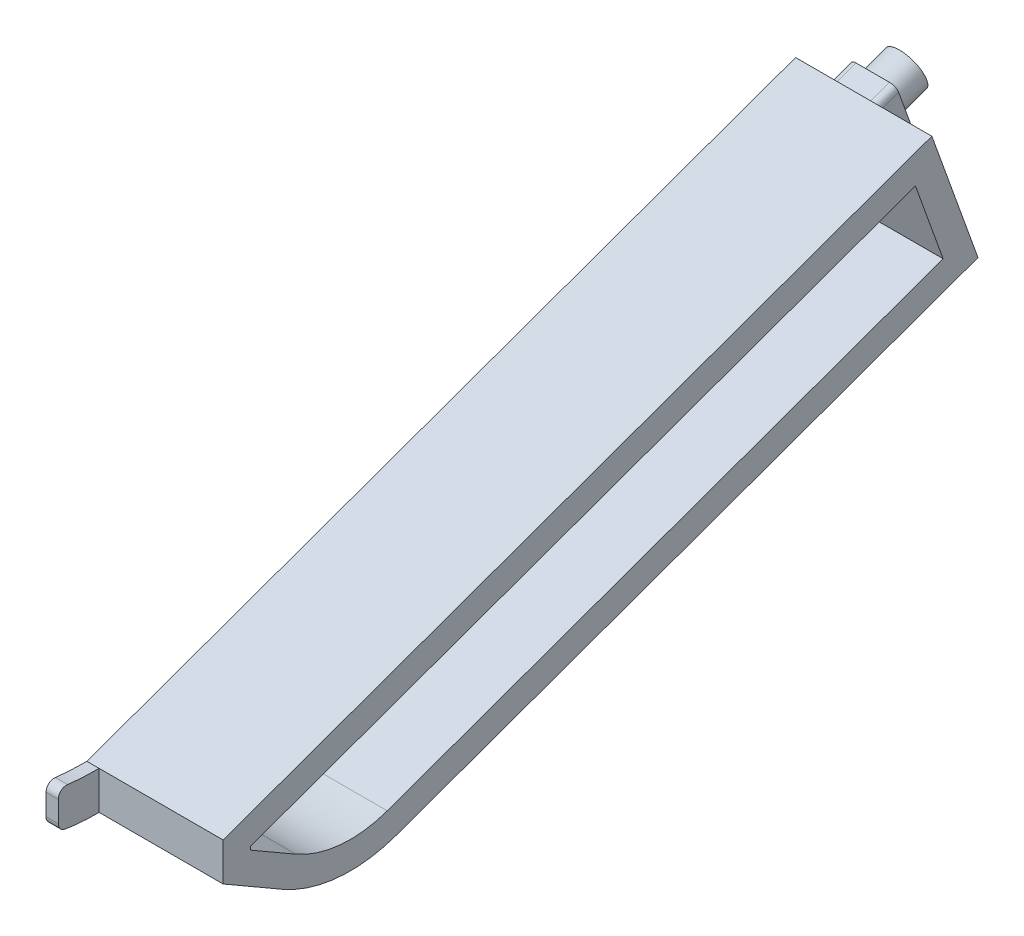
SolidWorks part; units mm, degrees
ref_plane "Front Plane" through (0, 0, 0) normal (0, 0, 1) x (1, 0, 0)
ref_plane "Top Plane" through (0, 0, 0) normal (0, 1, 0) x (1, 0, 0)
ref_plane "Right Plane" through (0, 0, 0) normal (1, 0, 0) x (0, 0, -1)
sketch "Sketch1" plane through (0, 0, 0) normal (1, 0, 0) x (0, 0, -1)
  line L0 (0, 2.8) -> (7.5715, 2.8) construction
  line L1 (-7, 5.1284) -> (-7, -2.9768) construction
  line L2 (0, 0) -> (0, -3.8905) construction
  line L3 (0, 2.8) -> (0, 0) construction
  line L4 (0, 0) -> (-8.3148, 0) construction
  line L5 (-3.7168, 0) -> (3.7562, 0) construction
  line L6 (0, 2.8) -> (-10.0538, 2.8) construction
  line L7 (2.921, 2.8) -> (-2.9257, 2.8) construction
  line L8 (0, 2.8) -> (0, 0)
  spline S0 degree 3 poles (0, 0) (-5.0883, 0) (-6.1015, 1.7391) (-7, 5.1284) knots 0 0 0 0 1 1 1 1
  spline S1 degree 3 poles (-7, 5.1284) (-4.5542, 3.4338) (-3.6542, 2.8) (0, 2.8) knots 0 0 0 0 1 1 1 1
  dimension "D1" = 2.8
  dimension "D2" = 7
extrude "Boss-Extrude1" add sketch "Sketch1" along normal blind 0.9
fillet "Fillet1" radius 0.5 1 edges at (0.45, 5.1284, 7)
sketch "Sketch3" plane through (0, 0, 0) normal (1, 0, 0) x (0, 0, -1)
  line L0 (0, 0) -> (40, 0)
  line L1 (40, 0) -> (40, 10)
  line L2 (40, 10) -> (20, 10)
  line L3 (20, 10) -> (0, 2.8)
  line L4 (0, 2.8) -> (0, 0)
  dimension "D1" = 10
  dimension "D2" = 40
  dimension "D3" = 20
extrude "Boss-Extrude2" add sketch "Sketch3" along normal blind 10
sketch "Sketch5" plane through (0, 0, 0) normal (1, 0, 0) x (0, 0, -1)
  line L0 (0, 0) -> (20, -11.547)
  line L1 (20, -11.547) -> (40, -11.547)
  line L2 (40, -11.547) -> (40, 0)
  line L3 (20, 10) -> (20, -11.547) construction
  line L4 (0, 0) -> (40, 0)
  dimension "D1" = 30
extrude "Boss-Extrude3" add sketch "Sketch5" along normal blind 10 contours L0 L1 L2 L4
sketch "Sketch4" plane through (10, 0, 0) normal (1, 0, 0) x (0, 0, -1)
  line L10 (2, 1.1547) -> (20.5359, -9.547)
  line L11 (38, -9.547) -> (38, 8)
  line L12 (38, 8) -> (20.349, 8)
  line L13 (20.349, 8) -> (2, 1.3943)
  line L15 (38, -9.547) -> (38, 8)
  line L16 (38, 8) -> (20.349, 8)
  line L17 (20.349, 8) -> (2, 1.3943)
  line L19 (2, 1.1547) -> (20.5359, -9.547)
  line L20 (20.5359, -9.547) -> (38, -9.547)
  line L21 (20.5359, -9.547) -> (38, -9.547)
  line L22 (2, 1.3943) -> (2, 1.1547)
  line L23 (2, 1.3943) -> (2, 1.1547)
  dimension "D1" = 2
extrude "Cut-Extrude1" [suppressed] cut sketch "Sketch4" against normal through all
sketch "Sketch6" plane through (10, 0, 0) normal (1, 0, 0) x (0, 0, -1)
  line L0 (8.3515, -4.8217) -> (55.3959, 12.1142)
  line L1 (0, 0) -> (20, -11.547) construction
  line L2 (55.3959, 12.1142) -> (52.0087, 21.5231)
  line L3 (52.0087, 21.5231) -> (20, 10)
  line L4 (20, 10) -> (8.3515, -4.8217)
  line L5 (20, 10) -> (0, 2.8) construction
  dimension "D1" = 10
  dimension "D2" = 50
extrude "Boss-Extrude4" add sketch "Sketch6" against normal up to surface (10 mm away) up to face at (0, 1.1472, -13.3733)
sketch "Sketch7" plane through (10, 0, 0) normal (1, 0, 0) x (0, 0, -1)
  line L0 (40, 6.5717) -> (-6.3967, -10.1311)
  line L1 (-6.3967, -10.1311) -> (25.0314, -20.3196)
  line L2 (25.0314, -20.3196) -> (52.5618, -5.852)
  line L3 (52.5618, -5.852) -> (40, 6.5717)
  line L4 (40, 6.5717) -> (55.3959, 12.1142) construction
extrude "Cut-Extrude2" cut sketch "Sketch7" against normal through all
fillet "Fillet2" radius 10 1 edges at (5, -4.8217, -8.3515)
sketch "Sketch8" plane through (10, 0, 0) normal (1, 0, 0) x (0, 0, -1)
  line L10 (2, 1.1547) -> (5.3316, -0.7688)
  line L11 (12.0414, -1.3677) -> (52.8366, 13.3186)
  line L12 (52.8366, 13.3186) -> (50.8043, 18.9639)
  line L13 (50.8043, 18.9639) -> (2, 1.3943)
  line L14 (2, 1.3943) -> (2, 1.1547)
  line L15 (2, 1.1547) -> (5.3316, -0.7688)
  line L16 (12.0414, -1.3677) -> (52.8366, 13.3186)
  line L17 (52.8366, 13.3186) -> (50.8043, 18.9639)
  line L18 (50.8043, 18.9639) -> (2, 1.3943)
  line L19 (2, 1.3943) -> (2, 1.1547)
  arc A2 (5.3316, -0.7688) -> (12.0414, -1.3677) centre (9.3316, 6.1594) ccw
  arc A3 (5.3316, -0.7688) -> (12.0414, -1.3677) centre (9.3316, 6.1594) ccw
  dimension "D1" = 2
extrude "Cut-Extrude3" cut sketch "Sketch8" against normal through all
sketch "Sketch9" plane through (0, 0, 0) normal (-1, 0, 0) x (0, 0, 1)
  line L0 (0, 0) -> (0, 9.0749) construction
  line L1 (0, 9.0749) -> (3, 9.0749) construction
  line L2 (3, 9.0749) -> (3, -2.6136) construction
  line L3 (3, -0.9887) -> (3, 5.799)
  line L4 (3, 5.799) -> (9.0916, 5.799)
  line L5 (9.0916, 5.799) -> (9.0916, -1.8537)
  line L6 (9.0916, -1.8537) -> (3, -0.9887)
  dimension "D1" = 3
extrude "Cut-Extrude4" cut sketch "Sketch9" against normal through all
fillet "Fillet3" radius 0.6 2 edges at (0.45, 0.2958, 3) (0.45, 3.0492, 3)
sketch "Sketch10" plane through (0, 19.0444, -52.901) normal (0, 0.3387, -0.9409) x (-1, 0, 0)
  line L0 (-5, 2.6345) -> (-5, -7.3655) construction
  line L1 (0, 2.6345) -> (-10, 2.6345) construction
  line L2 (0, -7.3655) -> (-10, -7.3655) construction
  line L3 (-5, -2.3655) -> (0, -2.3655) construction
  line L4 (0, 2.6345) -> (0, -7.3655) construction
  circle A0 centre (-5, -2.3655) radius 2.1
  dimension "D1" = 4.2
extrude "Boss-Extrude5" add sketch "Sketch10" along normal blind 3
sketch "Sketch11" plane through (0, 20.0605, -55.7237) normal (0, 0.3387, -0.9409) x (-1, 0, 0)
  circle A0 centre (-5, -2.3655) radius 1.5
  dimension "D1" = 3
extrude "Boss-Extrude6" add sketch "Sketch11" along normal blind 2
sketch "Sketch12" plane through (10, 0, 0) normal (1, 0, 0) x (0, 0, -1)
  line L0 (0, 2.8) -> (1.7953, -2.1324)
  line L1 (1.7953, -2.1324) -> (-2.7062, -1.6531)
  line L2 (-2.7062, -1.6531) -> (0, 2.8)
  line L3 (0, 2.8) -> (0, 0) construction
  dimension "D1" = 20
extrude "Cut-Extrude5" [suppressed] cut sketch "Sketch12" against normal up to surface (9.1 mm away) up to face at (0.9, 1.289, 1.8603)
split "Split1" bodies to split 110 resulting bodies 112 113 split by face at (5, 18.7945, -52.9909)
sketch "Sketch13" plane through (0, 19.0444, -52.901) normal (0, 0.3387, -0.9409) x (-1, 0, 0)
  line L0 (-10, -2.3655) -> (2.9298, -2.3655) construction
  line L1 (-10, -7.3655) -> (-10, 2.6345) construction
  line L2 (0, 2.6345) -> (0, -7.3655) construction
  line L3 (-3.4648, -4.0979) -> (0, -4.0979)
  line L4 (-3.4648, -4.0979) -> (-3.4648, -0.6331)
  line L5 (-3.4648, -0.6331) -> (0, -0.6331)
  line L6 (0, -4.0979) -> (0, -0.6331)
  line L7 (-3.4648, -4.0979) -> (0, -0.6331) construction
  line L8 (-3.4648, -0.6331) -> (0, -4.0979) construction
  circle A0 centre (-1.7324, -2.3655) radius 2.45 construction
  point P4 (-1.7324, -2.3655)
  dimension "D1" = 4.9
  dimension "D2" = 3.4648
extrude "Boss-Extrude7" add sketch "Sketch13" along normal up to surface (3 mm away) separate body up to face at (5, 19.2462, -56.0168)
sketch "Sketch14" plane through (0, 20.0605, -55.7237) normal (0, 0.3387, -0.9409) x (-1, 0, 0)
  line L0 (0, -2.3655) -> (-3.4648, -2.3655) construction
  line L1 (0, -4.0979) -> (0, -0.6331) construction
  line L2 (-3.4648, -0.6331) -> (-3.4648, -4.0979) construction
  circle A0 centre (-1.7324, -2.3655) radius 1.5
  dimension "D1" = 3
extrude "Boss-Extrude8" add sketch "Sketch14" along normal up to surface (2 mm away) separate body up to face at (5, 19.9236, -57.8986)
delete or keep bodies "Body-Delete/Keep 1" type delete bodies bodies 112
combine bodies "Combine1" operation type add bodies to combine 113 114 115
fillet "Fillet4" radius 0.5 4 edges at (3.4648, 15.6968, -55.7004) (0, 15.6968, -55.7004) (3.4648, 18.9568, -54.5268) (0, 18.9568, -54.5268)
